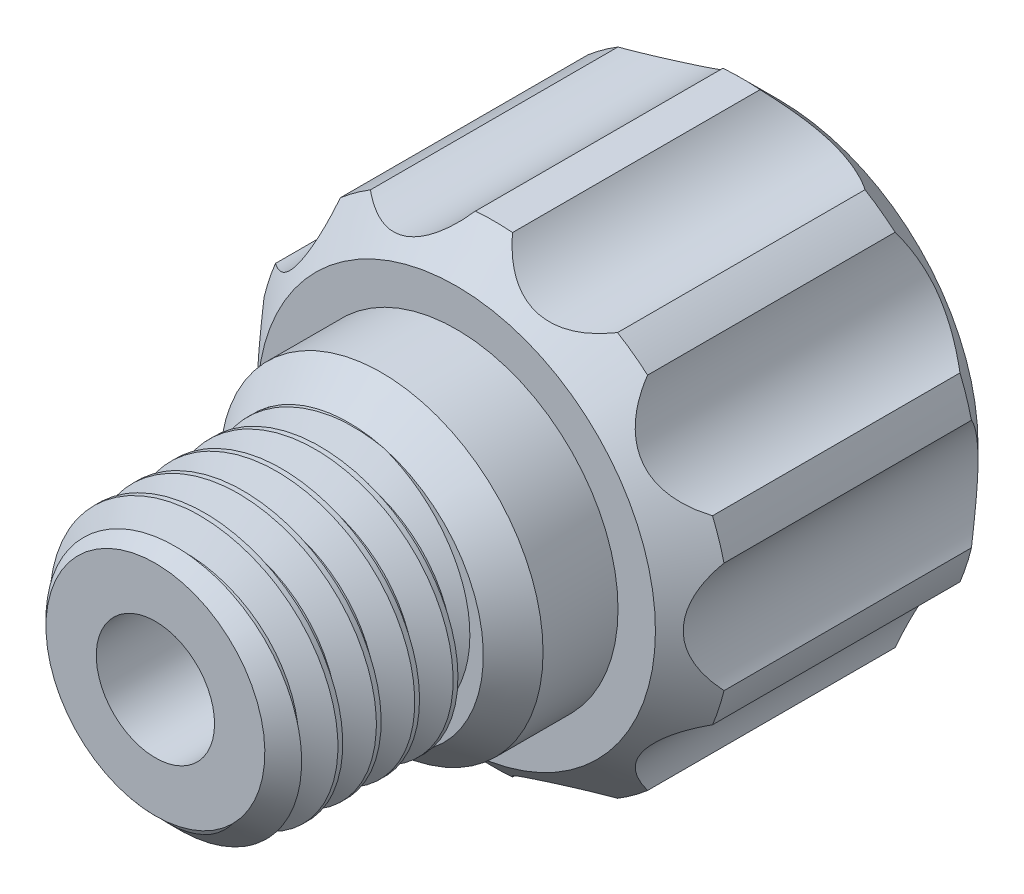
SolidWorks part; units mm, degrees
ref_plane "Front Plane" through (0, 0, 0) normal (0, 0, 1) x (1, 0, 0)
ref_plane "Top Plane" through (0, 0, 0) normal (0, 1, 0) x (1, 0, 0)
ref_plane "Right Plane" through (0, 0, 0) normal (1, 0, 0) x (0, 0, -1)
sketch "Sketch12" plane through (0, 0, 0) normal (1, 0, 0) x (0, 0, -1)
  line L0 (-7.9375, 0) -> (7.9375, 0) construction
  line L1 (-7.9375, 0) -> (-7.9375, 5.08) construction
  line L2 (-3.3655, 0) -> (-3.3655, 5.08) construction
  line L3 (7.9375, 0) -> (7.9375, 5.08) construction
  line L4 (-0.8255, 0) -> (-0.8255, 5.08) construction
  line L5 (6.7945, 0) -> (6.7945, 5.08) construction
  point P2 (0, 0)
  dimension "D1" = 5.08
ref_plane "Plane2" through (0, 0, 7.9375) normal (0, 0, -1) x (-1, 0, 0)
ref_plane "Plane3" through (0, 0, 3.3655) normal (0, 0, -1) x (-1, 0, 0)
ref_plane "Plane4" through (0, 0, 0.8255) normal (0, 0, -1) x (-1, 0, 0)
ref_plane "Plane5" through (0, 0, -7.9375) normal (0, 0, -1) x (-1, 0, 0)
sketch "Sketch1" plane through (0, 0, 7.9375) normal (0, 0, 1) x (1, 0, 0)
  line L0 (0, 3.175) -> (0, -3.175) construction
  circle A0 centre (0, 0) radius 3.175
  dimension "OD" = 6.35
extrude "Extrude1" add sketch "Sketch1" against normal up to surface (4.572 mm away) up to plane "Plane3"
sketch "Sketch2" plane through (0, 0, 7.9375) normal (0, 0, 1) x (1, 0, 0)
  circle A0 centre (0, 0) radius 3.175 construction
  circle A1 centre (0, 0) radius 3.175
curve "Helix/Spiral1" pitch 0.9071 height 5.4791 radius 3.175 centre (0, 0, 7.9375) axis (0, 0, -1) start towards (0, 1, 0) parameters "pitch"=0.9071
sketch "Sketch3" plane through (0, 0, 0) normal (1, 0, 0) x (0, 0, -1)
  line L0 (-8.7312, 3.175) -> (-8.3911, 2.5858)
  line L1 (-8.3911, 2.5858) -> (-8.2777, 2.5858)
  line L2 (-8.2777, 2.5858) -> (-7.9375, 3.175)
  line L3 (-8.7312, 3.175) -> (-7.9375, 3.175)
  line L4 (-8.3344, 3.175) -> (-8.3344, 2.5858) construction
  line L5 (-8.5612, 2.8804) -> (-8.1076, 2.8804) construction
  line L6 (-7.9375, 3.175) -> (-7.9375, -3.175) construction
  dimension "D1" = 0.1134
  dimension "D2" = 0.4536
  dimension "D3" = 60
sweep "Cut-Sweep1" cut profiles "Sketch3" path "Helix/Spiral1" align with end faces yes
sketch "Sketch6" plane through (0, 0, 0.8255) normal (0, 0, -1) x (-1, 0, 0)
  line L0 (0, 0) -> (0, 5.588) construction
  line L1 (-0.4384, 5.5708) -> (0.4384, 5.5708) construction
  line L2 (0, 0) -> (-0.4384, 5.5708) construction
  line L3 (0, 0) -> (-2.9197, 4.7646) construction
  line L4 (-3.2845, 4.5208) -> (-2.9561, 4.0687) construction
  circle A0 centre (0, 0) radius 5.588 construction
  arc A1 (-0.4384, 5.5708) -> (0.4384, 5.5708) centre (0, 0) cw
  arc A2 (-0.4384, 5.5708) -> (-2.9197, 4.7646) centre (-2.2668, 6.9763) cw
  circle A3 centre (0, 0) radius 5.0292 construction
  arc A4 (2.9197, 4.7646) -> (3.6291, 4.2491) centre (0, 0) cw
  arc A5 (2.9197, 4.7646) -> (0.4384, 5.5708) centre (2.2668, 6.9763) cw
  arc A6 (5.1626, 2.1384) -> (5.4336, 1.3045) centre (0, 0) cw
  arc A7 (5.1626, 2.1384) -> (3.6291, 4.2491) centre (5.9344, 4.3116) cw
  arc A8 (5.4336, -1.3045) -> (5.1626, -2.1384) centre (0, 0) cw
  arc A9 (5.4336, -1.3045) -> (5.4336, 1.3045) centre (7.3354, 0) cw
  arc A10 (3.6291, -4.2491) -> (2.9197, -4.7646) centre (0, 0) cw
  arc A11 (3.6291, -4.2491) -> (5.1626, -2.1384) centre (5.9344, -4.3116) cw
  arc A12 (0.4384, -5.5708) -> (-0.4384, -5.5708) centre (0, 0) cw
  arc A13 (0.4384, -5.5708) -> (2.9197, -4.7646) centre (2.2668, -6.9763) cw
  arc A14 (-2.9197, -4.7646) -> (-3.6291, -4.2491) centre (0, 0) cw
  arc A15 (-2.9197, -4.7646) -> (-0.4384, -5.5708) centre (-2.2668, -6.9763) cw
  arc A16 (-5.1626, -2.1384) -> (-5.4336, -1.3045) centre (0, 0) cw
  arc A17 (-5.1626, -2.1384) -> (-3.6291, -4.2491) centre (-5.9344, -4.3116) cw
  arc A18 (-5.4336, 1.3045) -> (-5.1626, 2.1384) centre (0, 0) cw
  arc A19 (-5.4336, 1.3045) -> (-5.4336, -1.3045) centre (-7.3354, 0) cw
  arc A20 (-3.6291, 4.2491) -> (-2.9197, 4.7646) centre (0, 0) cw
  arc A21 (-3.6291, 4.2491) -> (-5.1626, 2.1384) centre (-5.9344, 4.3116) cw
  dimension "D2" = 10.0584
  dimension "Body OD" = 11.176
  dimension "D1" = 4.5
  dimension "D3" = 27
  dimension "Wall Ref" = 0.5588
  dimension "D4" = 10
extrude "Extrude2" add sketch "Sketch6" along normal up to vertex (7.62 mm away) up to point (0, 5.08, -6.7945)
sketch "Sketch10" plane through (0, 0, -6.7945) normal (0, 0, -1) x (-1, 0, 0)
  line L0 (-0.4384, 5.5708) -> (0.4384, 5.5708) construction
  line L1 (0, 5.5708) -> (0, 4.6939) construction
  line L2 (0, 4.6939) -> (0, 3.8171) construction
  circle A0 centre (0, 0) radius 3.8171
ref_plane "Plane1" through (0, 0, -0.2921) normal (0, 0, 1) x (1, 0, 0)
extrude "Cut-Extrude1" cut sketch "Sketch10" against normal up to surface (6.5024 mm away) up to plane "Plane1"
sketch "Sketch11" plane through (0, 0, -7.9375) normal (0, 0, -1) x (-1, 0, 0)
  circle A0 centre (0, 0) radius 2.0574
  dimension "Internal Barb OD" = 4.1148
extrude "Boss-Extrude2" add sketch "Sketch11" against normal up to body draft 1 separate body draft outward yes
sketch "Sketch18" plane through (0, 0, 0.8255) normal (0, 0, 1) x (1, 0, 0)
  line L0 (-5.3145, 1.7268) -> (-3.6302, 1.1795) construction
  circle A0 centre (0, 0) radius 3.8171 construction
  circle A1 centre (0, 0) radius 3.8171
  arc A2 (-5.1626, 2.1384) -> (-5.4336, 1.3045) centre (0, 0) ccw construction
  dimension "D1" = 1.7709
extrude "Boss-Extrude3" add sketch "Sketch18" along normal blind 1.7709
sketch "Sketch13" plane through (0, 0, 3.3655) normal (0, 0, -1) x (-1, 0, 0)
  circle A1 centre (0, 0) radius 3.175
  circle A2 centre (0, 0) radius 3.175
  dimension "D1" = 0
sketch "Sketch14" plane through (0, 0, 2.5964) normal (0, 0, 1) x (1, 0, 0)
  circle A0 centre (0, 0) radius 5.0292 construction
  arc A1 (-0.4384, -5.5708) -> (-2.9197, -4.7646) centre (-2.2668, -6.9763) ccw construction
  circle A2 centre (0, 0) radius 3.8171
  circle A3 centre (0, 0) radius 3.8171 construction
sketch "Sketch15" plane through (0, 0, 0) normal (1, 0, 0) x (0, 0, -1)
  line L0 (-3.3655, 0) -> (-3.3655, 3.175)
  line L1 (-3.3655, 3.175) -> (-2.5964, 3.8171)
  line L2 (-2.5964, 3.8171) -> (-2.5964, 0)
  line L3 (-7.9375, 0) -> (7.9375, 0) construction
  line L9 (-3.3655, 0) -> (-2.5964, 0)
revolve "Revolve1" add sketch "Sketch15" angle 360 mid plane about L0
sketch "Sketch16" plane through (0, 0, 7.9375) normal (0, 0, 1) x (1, 0, 0)
  circle A0 centre (0, 0) radius 1.397
  dimension "D1" = 2.794
extrude "Cut-Extrude2" cut sketch "Sketch16" against normal through all
sketch "Sketch17" plane through (0, 0, 7.9375) normal (0, 0, 1) x (1, 0, 0)
  line L0 (0, 3.175) -> (0, 2.5858) construction
  line L1 (0, 3.175) -> (0, 2.5858) construction
  circle A0 centre (0, 0) radius 2.5858
extrude "Cut-Extrude3" cut sketch "Sketch17" against normal blind 2.54 draft 45 flip side to cut
sketch "Sketch19" plane through (0, 0, 0) normal (1, 0, 0) x (0, 0, -1)
  line L0 (6.7945, 4.7011) -> (5.9076, 5.588)
  line L1 (6.7945, 4.6702) -> (6.7945, 5.5708) construction
  line L2 (6.7945, 5.588) -> (-0.8255, 5.588) construction
  line L3 (5.9076, 5.588) -> (6.7945, 5.588)
  line L4 (6.7945, 5.588) -> (6.7945, 4.7011)
  line L5 (6.7945, 4.2491) -> (6.7945, 4.7646) construction
  line L6 (2.9845, 5.5708) -> (2.9845, 0.4746) construction
  line L7 (6.7945, 5.5708) -> (-0.8255, 5.5708) construction
  line L8 (-0.8255, 5.588) -> (-0.8255, 4.7011)
  line L9 (0.0614, 5.588) -> (-0.8255, 5.588)
  line L10 (-0.8255, 4.7011) -> (0.0614, 5.588)
  dimension "D1" = 45
  dimension "D2" = 0.0635
revolve "Cut-Revolve1" cut sketch "Sketch19" angle 360 mid plane about L0
equation "\"D3@Helix/Spiral1\" = \"Thread Boss@Sketch12\"+\"pitch@Helix/Spiral1\""
equation "\"D1@Sketch3\" = \"pitch@Helix/Spiral1\"*.125"
equation "\"D2@Sketch3\" = \"pitch@Helix/Spiral1\"*.5"
equation "\"D2@Sketch6\" = \"Body OD@Sketch6\"*.9"
equation "\"D1@Plane1\" = \"Wall Ref@Sketch6\" *2"
equation "\"D1@Boss-Extrude3\" = \"D1@Sketch18\""
